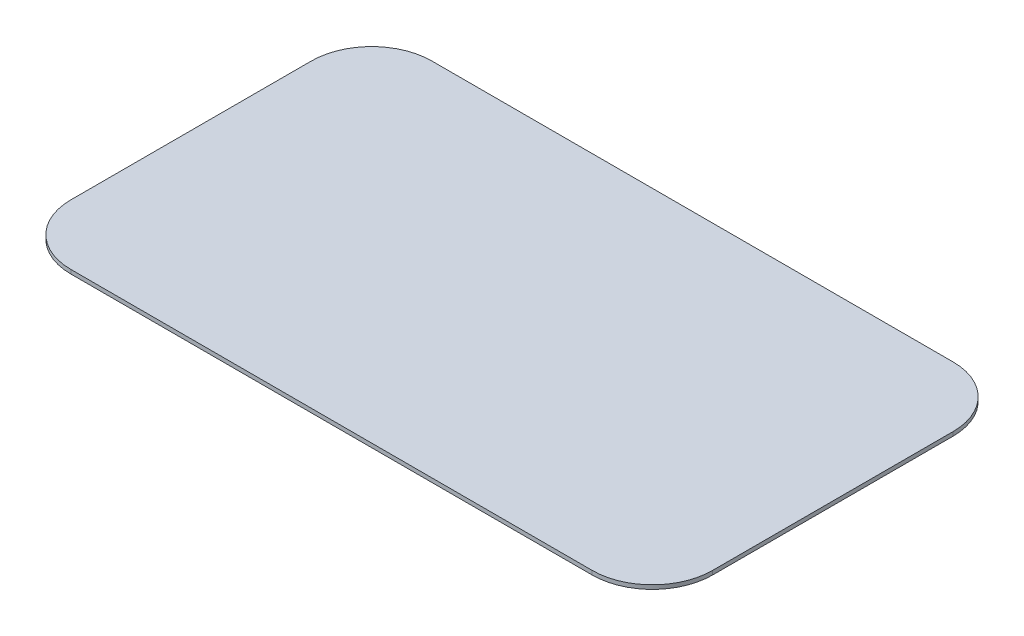
SolidWorks part; units mm, degrees
ref_plane "Front Plane" through (0, 0, 0) normal (0, 0, 1) x (1, 0, 0)
ref_plane "Top Plane" through (0, 0, 0) normal (0, 1, 0) x (1, 0, 0)
ref_plane "Right Plane" through (0, 0, 0) normal (1, 0, 0) x (0, 0, -1)
sketch "Sketch1" plane through (0, 0, 0) normal (0, 1, 0) x (1, 0, 0)
  line L1 (-6.5, -4.5) -> (6.5, -4.5)
  line L2 (-8, -3) -> (-8, 3)
  line L3 (-6.5, 4.5) -> (6.5, 4.5)
  line L4 (8, -3) -> (8, 3)
  line L5 (-8, -4.5) -> (8, 4.5) construction
  line L6 (-8, 4.5) -> (8, -4.5) construction
  arc A0 (-8, -3) -> (-6.5, -4.5) centre (-6.5, -3) ccw
  arc A1 (-6.5, 4.5) -> (-8, 3) centre (-6.5, 3) ccw
  arc A2 (8, -3) -> (6.5, -4.5) centre (6.5, -3) cw
  arc A3 (8, 3) -> (6.5, 4.5) centre (6.5, 3) ccw
  point P0 (0, 0)
  dimension "D3" = 1.5
  dimension "D1" = 16
  dimension "D2" = 9
extrude "Boss-Extrude1" add sketch "Sketch1" along normal blind 0.1
